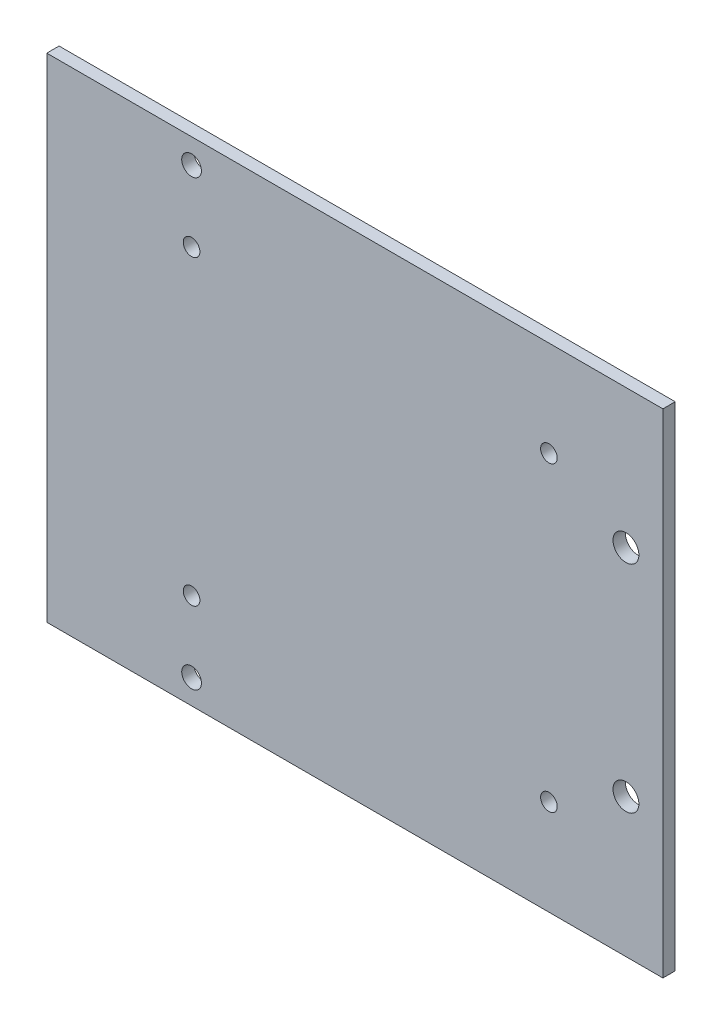
SolidWorks part; units mm, degrees
ref_plane "前视基准面" through (0, 0, 0) normal (0, 0, 1) x (1, 0, 0)
ref_plane "上视基准面" through (0, 0, 0) normal (0, 1, 0) x (1, 0, 0)
ref_plane "右视基准面" through (0, 0, 0) normal (1, 0, 0) x (0, 0, -1)
sketch "草图1" plane through (0, 0, 0) normal (0, 0, 1) x (1, 0, 0)
  line L1 (-50, 40) -> (50, 40)
  line L2 (-50, 40) -> (-50, -40)
  line L3 (-50, -40) -> (50, -40)
  line L4 (50, 40) -> (50, -40)
  line L5 (-50, 40) -> (50, -40) construction
  line L6 (-50, -40) -> (50, 40) construction
  point P0 (0, 0)
  dimension "D1" = 80
  dimension "D2" = 100
extrude "凸台-拉伸1" add sketch "草图1" along normal blind 2
sketch "草图3" plane through (0, 0, 2) normal (0, 0, 1) x (1, 0, 0)
  line L0 (-50, 0) -> (50, 0) construction
  line L1 (-26.5, -40) -> (-26.5, 40) construction
  line L2 (2.5, -40) -> (2.5, 40) construction
  line L4 (50, -40) -> (50, 40)
  line L5 (50, 40) -> (-50, 40)
  line L6 (-50, 40) -> (-50, -40)
  line L7 (-50, -40) -> (50, -40)
  line L8 (50, -40) -> (50, 40)
  line L9 (50, 40) -> (-50, 40)
  line L10 (-50, 40) -> (-50, -40)
  line L11 (-50, -40) -> (50, -40)
  circle A0 centre (-26.5, -24.5) radius 1.35
  circle A1 centre (-26.5, 24.5) radius 1.35
  circle A2 centre (31.5, 24.5) radius 1.35
  circle A3 centre (31.5, -24.5) radius 1.35
  dimension "D3" = 2.7
  dimension "D4" = 49
  dimension "D5" = 58
  dimension "D2" = 23.5
  dimension "D1" = 0
extrude "切除-拉伸1" cut sketch "草图3" against normal through all contours A0 | A1 | A2 | A3 region at (-26.5, -24.5, 2) region at (-26.5, 24.5, 2) region at (31.5, 24.5, 2) region at (31.5, -24.5, 2)
sketch "草图4" plane through (0, 0, 0) normal (0, 0, -1) x (-1, 0, 0)
  circle A0 centre (26.5, -36) radius 1.6 construction
  circle A1 centre (26.5, -36) radius 1.6
extrude "切除-拉伸2" cut sketch "草图4" against normal through all
sketch "草图5" plane through (0, 0, 2) normal (0, 0, 1) x (1, 0, 0)
  line L0 (-26.5, 23.15) -> (-26.5, 40) construction
  line L4 (50, -40) -> (50, 40)
  line L5 (50, 40) -> (-50, 40)
  line L6 (-50, 40) -> (-50, -40)
  line L7 (-50, -40) -> (50, -40)
  line L8 (50, -40) -> (50, 40)
  line L9 (50, 40) -> (-50, 40)
  line L10 (-50, 40) -> (-50, -40)
  line L11 (-50, -40) -> (50, -40)
  circle A0 centre (-26.5, 24.5) radius 1.35 construction
  circle A1 centre (-26.5, 36) radius 1.6
  dimension "D2" = 3.2
  dimension "D3" = 11.5
  dimension "D1" = 0
extrude "切除-拉伸3" cut sketch "草图5" against normal through all contours A1
sketch "草图7" plane through (0, 0, 2) normal (0, 0, 1) x (1, 0, 0)
  line L0 (50, 0) -> (-50, 0) construction
  line L1 (44, 40) -> (44, -40) construction
  line L4 (50, -40) -> (50, 40)
  line L5 (50, 40) -> (-50, 40)
  line L6 (-50, 40) -> (-50, -40)
  line L7 (-50, -40) -> (50, -40)
  line L8 (50, -40) -> (50, 40)
  line L9 (50, 40) -> (-50, 40)
  line L10 (-50, 40) -> (-50, -40)
  line L11 (-50, -40) -> (50, -40)
  circle A0 centre (44, 17.5) radius 2.1
  circle A1 centre (44, -17.5) radius 2.1
  dimension "D3" = 4.2
  dimension "D4" = 35
  dimension "D2" = 6
  dimension "D1" = 0
extrude "切除-拉伸5" cut sketch "草图7" against normal blind 10 contours A0 | A1 region at (44, 17.5, 2) region at (44, -17.5, 2)
